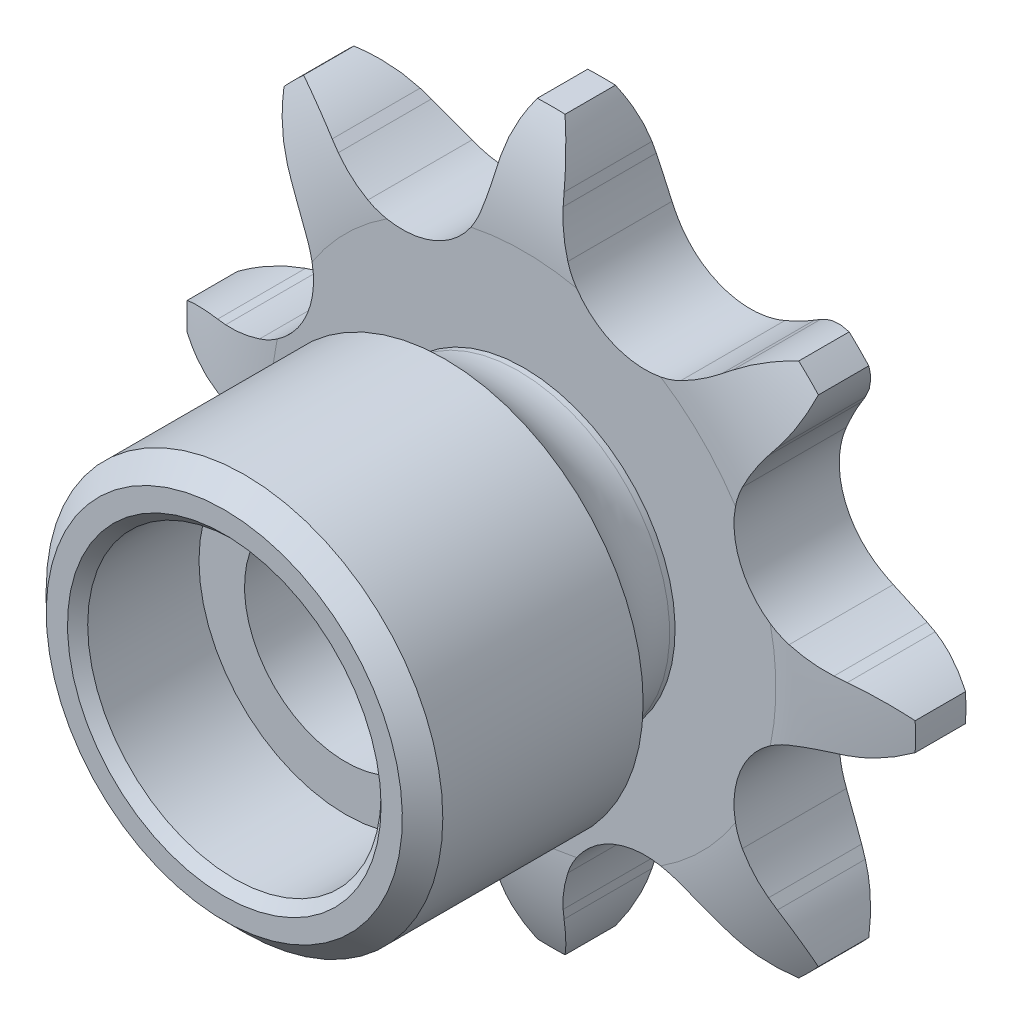
SolidWorks part; units mm, degrees
ref_plane "Front Plane" through (0, 0, 0) normal (0, 0, 1) x (1, 0, 0)
ref_plane "Top Plane" through (0, 0, 0) normal (0, 1, 0) x (1, 0, 0)
ref_plane "Right Plane" through (0, 0, 0) normal (1, 0, 0) x (0, 0, -1)
sketch "Sketch0" plane through (0, 0, 0) normal (0, 0, 1) x (1, 0, 0)
  line L0 (3, -7.2426) -> (0, 0) construction
  line L1 (0, 0) -> (7.2426, -3) construction
  line L2 (0, 0) -> (-3, -7.2426) construction
  line L3 (3, -7.2426) -> (7.2426, -3) construction
  line L4 (3, -7.2426) -> (-3, -7.2426) construction
  line L5 (4.9471, -6.053) -> (4.7324, -5.897)
  line L6 (3, -7.2426) -> (0, -8.4853) construction
  line L7 (0.782, -7.7783) -> (0.8235, -7.5161)
  line L8 (0, -7.2426) -> (0, -9.0426) construction
  line L9 (3.8656, -5.3864) -> (1.6476, -10.1428) construction
  line L10 (0, 0) -> (0, -7.2426) construction
  line L11 (4.7324, -5.897) -> (1.6476, -10.1428) construction
  line L12 (0, -9.0426) -> (0, -9.4708) construction
  line L13 (6.9598, -3.2828) -> (4.9471, -6.053) construction
  circle A0 centre (0, 0) radius 9.0426 construction
  circle A1 centre (0, 0) radius 7.8394 construction
  arc A2 (-3.7569, -10.4654) -> (10.0567, -4.7436) centre (0, 0) ccw
  circle A3 centre (0, 0) radius 9.4708 construction
  circle A4 centre (3, -7.2426) radius 2 construction
  arc A7 (3.8656, -5.3864) -> (1.0754, -6.5421) centre (3, -7.2426) ccw
  circle A8 centre (3, -7.2426) radius 2.0481 construction
  arc A9 (4.9471, -6.053) -> (10.0567, -4.7436) centre (6.9598, -3.2828) ccw
  arc A10 (4.7324, -5.897) -> (3.8656, -5.3864) centre (1.6476, -10.1428) ccw
  arc A11 (0.782, -7.7783) -> (-3.7569, -10.4654) centre (-2.6, -7.2426) cw
  arc A12 (0.8235, -7.5161) -> (1.0754, -6.5421) centre (6.007, -8.3371) cw
  dimension "D1" = 2.0481
  dimension "R" = 2.0481
sketch "Sketch1" plane through (0, 0, 0) normal (1, 0, 0) x (0, 0, -1)
  line L0 (1.3, 0) -> (-1.3, 0)
  line L1 (-1.3, 0) -> (-1.3, 6.2302)
  line L2 (-1.3, 7.8394) -> (0, 7.8394) construction
  line L3 (-0.6, 9.0426) -> (0.6, 9.0426)
  line L5 (1.3, 6.2302) -> (1.3, 0)
  line L7 (0, 9.0426) -> (0, 0) construction
  line L8 (-1.3, 6.2302) -> (1.3, 6.2302) construction
  line L9 (0, 9.0426) -> (0, -9.0426) construction
  line L10 (-1.3, 6.2302) -> (-1.3, 9.0426) construction
  line L11 (-1.3, 9.0426) -> (-0.6, 9.0426) construction
  line L12 (0.6, 9.0426) -> (1.3, 9.0426) construction
  line L13 (1.3, 9.0426) -> (1.3, 6.2302) construction
  line L14 (0, 0) -> (-6.4008, 0) construction
  line L15 (-1.3, 7.8394) -> (-1.3, 3.7394) construction
  line L22 (1.3, 0) -> (-8.7, 0) construction
  line L24 (-1.3, 0) -> (-1.3, 3.7394) construction
  arc A0 (-0.6, 9.0426) -> (-1.3, 6.2302) centre (4.7, 6.2302) ccw
  arc A1 (0.6, 9.0426) -> (1.3, 6.2302) centre (-4.7, 6.2302) cw
  dimension "R" = 6
revolve "Revolve1" add sketch "Sketch1" angle 360 mid plane about L0
extrude "Cut-Extrude1" cut sketch "Sketch0" against normal through all and the other way through all
pattern_circular "CirPattern1" count 8 over 360 about axis through (0, 0, -1.3) along (0, 0, -1) of "Cut-Extrude1"
sketch "Sketch2" plane through (0, 0, 0) normal (0, 0, 1) x (1, 0, 0)
  circle A0 centre (0, 0) radius 2.5 construction
  circle A1 centre (0, 0) radius 4.9
  circle A2 centre (0, 0) radius 9 construction
  dimension "Bore" = 5
  dimension "Hub Dia." = 9.8
  dimension "OD" = 18
extrude "Boss-Extrude1" add sketch "Sketch2" along normal up to vertex (8.7 mm away) from surface up to point (0, 0, 8.7) starting at face at (0, 0, 1.3)
sketch "Sketch3" plane through (0, 0, 0) normal (0, 0, 1) x (1, 0, 0)
  circle A0 centre (0, 0) radius 2.5 construction
  circle A1 centre (0, 0) radius 2.5
extrude "Cut-Extrude2" cut sketch "Sketch3" along normal through all and the other way through all
sketch "Sketch4" plane through (0, 0, 0) normal (1, 0, 0) x (0, 0, -1)
  line L0 (-8.7, 4.9) -> (-8.7, 4.4)
  line L1 (-1.3, 9.0426) -> (-3.25, 9.0426)
  line L2 (-1.3, 9.0426) -> (-1.3, 3.7394)
  line L3 (-1.3, 3.7394) -> (-3.25, 3.7394)
  line L4 (-3.25, 9.0426) -> (-3.25, 3.7394)
  line L9 (-8.7, 4.4) -> (-8.2, 4.9)
  line L10 (-8.2, 4.9) -> (-8.7, 4.9)
  dimension "C" = 0.5
  dimension "D3" = 1.95
revolve "Cut-Revolve1" cut sketch "Sketch4" angle 360 mid plane about L22
sketch "Sketch5" plane through (0, 0, 0) normal (0, 0, 1) x (1, 0, 0)
  circle A0 centre (0, 0) radius 9 construction
  circle A1 centre (0, 0) radius 9
extrude "Cut-Extrude3" cut sketch "Sketch5" against normal through all and the other way through all flip side to cut
sketch "Sketch6" plane through (0, 0, 8.7) normal (0, 0, 1) x (1, 0, 0)
  circle A0 centre (0, 0) radius 3.625
  dimension "D1" = 7.25
extrude "Cut-Extrude4" cut sketch "Sketch6" against normal blind 3
sketch "Sketch7" plane through (0, 0, -1.3) normal (0, 0, -1) x (-1, 0, 0)
  circle A0 centre (0, 0) radius 3.625
  dimension "D1" = 7.25
extrude "Cut-Extrude5" cut sketch "Sketch7" against normal blind 1.5
chamfer "Chamfer1" distance 0.25 angle 45 1 edges at (3.625, 0, 8.7)
sketch "Sketch8" plane through (0, 0, -1.3) normal (0, 0, -1) x (-1, 0, 0)
  circle A0 centre (0, 0) radius 3.625
  circle A2 centre (0, 0) radius 4.2
  dimension "D1" = 7.25
  dimension "D2" = 8.4
fillet "Fillet3" radius 2 1 edges at (0, 3.7394, 3.25)
equation "\"360/N@Sketch0\" = 360/\"Teeth@CirPattern1\""
equation "\"Ds@Sketch0\" = 1.005 * \"Dr@Sketch0\" + ( 0.003 * 25.4 ) "
equation "\"R@Sketch0\" = 1/2 * \"Ds@Sketch0\""
equation "\"A@Sketch0\" = 35 +  ( 60 / \"Teeth@CirPattern1\" ) "
equation "\"B@Sketch0\" = 18 -  ( 56 / \"Teeth@CirPattern1\" )"
equation "\"ac@Sketch0\" = 0.8 * \"Dr@Sketch0\""
equation "\"ab@Sketch0\" = 1.4 * \"Dr@Sketch0\""
equation "\"J@Sketch0\" = 0.3 * \"Pitch@Sketch0\""
equation "\"D3@Sketch4\" = \"t@Sketch1\" * 3 / 4"
